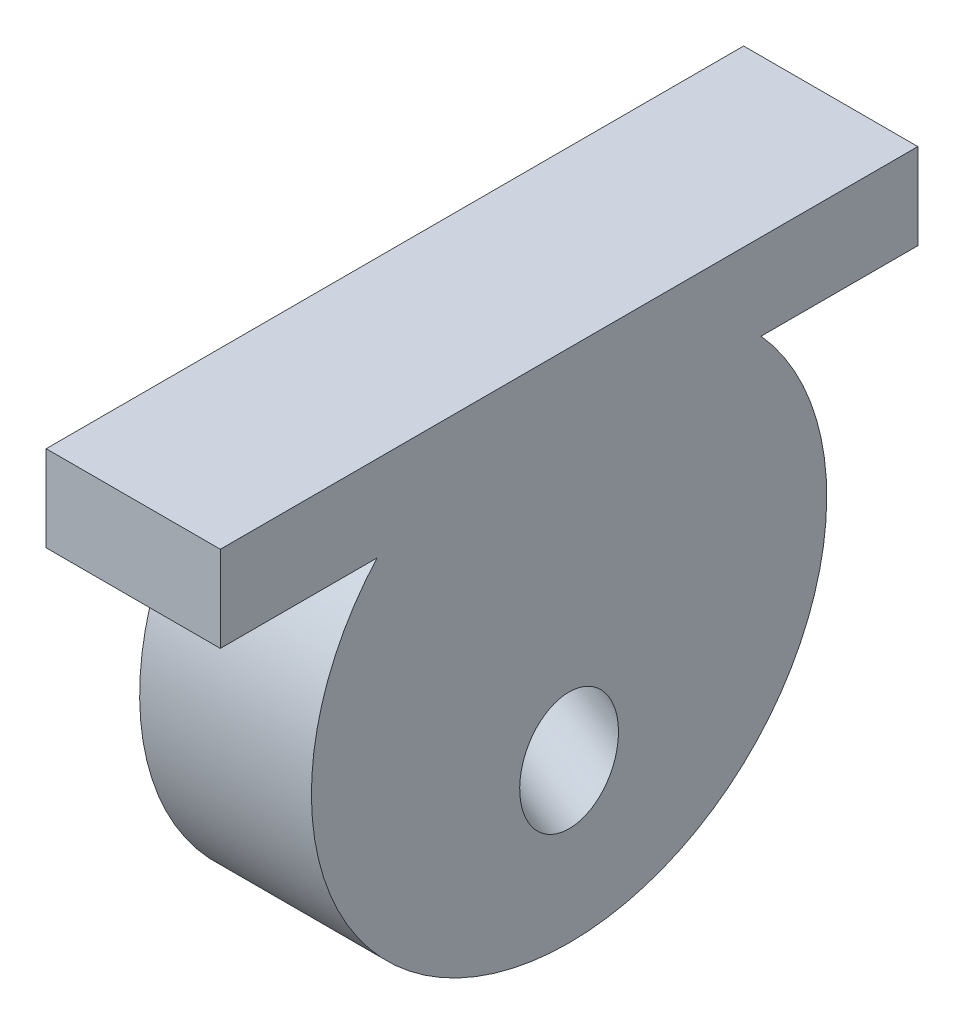
SolidWorks part; units mm, degrees
ref_plane "Front Plane" through (0, 0, 0) normal (0, 0, 1) x (1, 0, 0)
ref_plane "Top Plane" through (0, 0, 0) normal (0, 1, 0) x (1, 0, 0)
ref_plane "Right Plane" through (0, 0, 0) normal (1, 0, 0) x (0, 0, -1)
sketch "Sketch3" plane through (0, 717.6366, 0) normal (0, -1, 0) x (-1, 0, 0)
  line L0 (-524.1514, -762.9166) -> (-524.1514, -558.1792) construction
  line L1 (-524.1514, -712.1166) -> (-498.3984, -712.1166)
  line L2 (-524.1514, -712.1166) -> (-524.1514, -608.9792)
  line L3 (-524.1514, -608.9792) -> (-498.3984, -608.9792)
  line L4 (-498.3984, -712.1166) -> (-498.3984, -608.9792)
  line L5 (-498.3984, -762.9166) -> (-498.3984, -558.1792) construction
  line L6 (-524.1514, -762.9166) -> (-498.3984, -762.9166) construction
  line L7 (-524.1514, -558.1792) -> (-498.3984, -558.1792) construction
  dimension "D1" = 50.8
  dimension "D2" = 50.8
extrude "Boss-Extrude1" add sketch "Sketch3" along normal blind 12.7
sketch "Sketch4" plane through (524.1514, 0, 0) normal (1, 0, 0) x (0, 0, -1)
  line L0 (-660.5479, 717.6366) -> (-660.5479, 679.5366) construction
  line L1 (-608.9792, 717.6366) -> (-712.1166, 717.6366) construction
  circle A0 centre (-660.5479, 679.5366) radius 38.1
  dimension "D1" = 38.1
extrude "Boss-Extrude2" add sketch "Sketch4" against normal blind 25.4
sketch3d "3DSketch2"
  line L0 (524.1514, 717.6366, 660.5479) -> (524.1514, 641.4366, 660.5479) construction
  line L1 (524.1514, 717.6366, 608.9792) -> (524.1514, 717.6366, 712.1166) construction
  line L2 (498.3984, 717.6366, 660.5479) -> (498.7514, 641.4366, 660.5479) construction
  line L3 (498.3984, 717.6366, 712.1166) -> (498.3984, 717.6366, 608.9792) construction
  line L4 (570.6086, 634.0665, 660.5479) -> (477.6943, 695.5716, 660.5479)
  arc A0 (524.1514, 704.9366, 688.946) -> (524.1514, 704.9366, 632.1499) centre (524.1514, 679.5366, 660.5479) ccw construction
  arc A1 (498.7514, 704.9366, 688.946) -> (498.7514, 704.9366, 632.1499) centre (498.7514, 679.5366, 660.5479) ccw construction
  point P7 (562.2514, 679.5366, 660.5479)
  point P15 (536.8514, 679.5366, 660.5479)
  point P19 (524.1514, 664.8191, 660.5479)
sweep "Cut-Sweep1" cut path "3DSketch2" circular profile diameter 14.605 parameters "D3"=14.605
